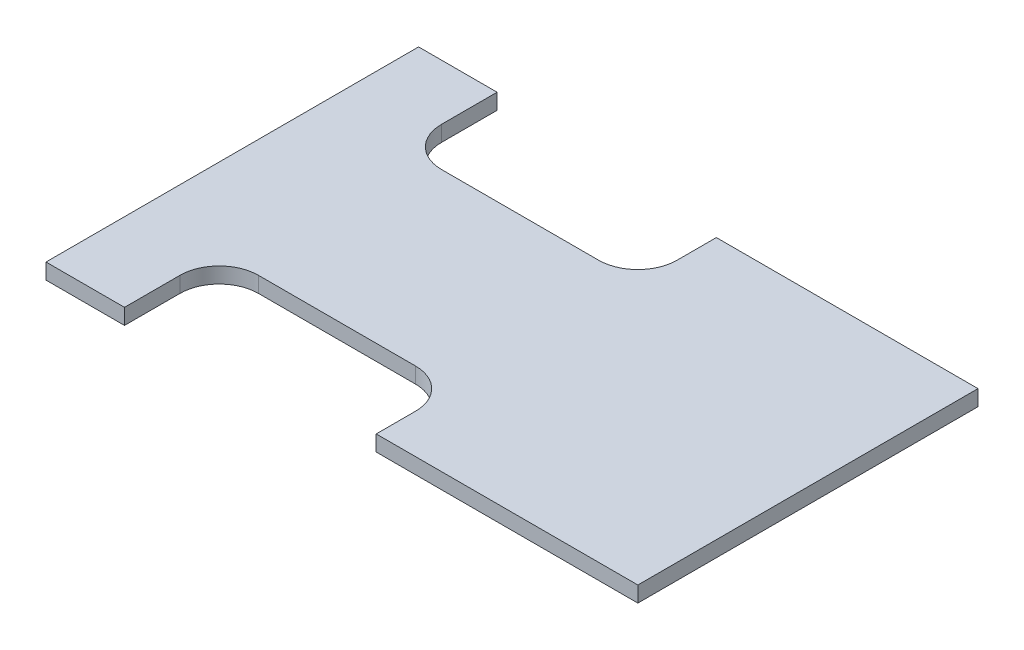
SolidWorks part; units mm, degrees
material "ABS"
ref_plane "Front Plane" through (0, 0, 0) normal (0, 0, 1) x (1, 0, 0)
ref_plane "Top Plane" through (0, 0, 0) normal (0, 1, 0) x (1, 0, 0)
ref_plane "Right Plane" through (0, 0, 0) normal (1, 0, 0) x (0, 0, -1)
sketch "Sketch1" plane through (0, 0, 0) normal (0, 1, 0) x (1, 0, 0)
  line L1 (-110, 65) -> (110, 65)
  line L2 (-110, 65) -> (-110, -65)
  line L3 (-110, -65) -> (110, -65)
  line L4 (110, 65) -> (110, -65)
  line L5 (-110, 65) -> (110, -65) construction
  line L6 (-110, -65) -> (110, 65) construction
  point P0 (0, 0)
  dimension "D1" = 220
  dimension "D2" = 130
extrude "Boss-Extrude1" add sketch "Sketch1" along normal blind 6
sketch "Sketch2" plane through (0, 6, 0) normal (0, 1, 0) x (1, 0, 0)
  line L0 (-110, -65) -> (-80, -65) construction
  line L1 (-110, -65) -> (110, -65) construction
  line L2 (0, 0) -> (-110, 0) construction
  line L3 (-80, -65) -> (10, -65)
  line L4 (-80, -65) -> (-80, -35)
  line L5 (-80, -35) -> (10, -35)
  line L6 (10, -65) -> (10, -35)
  line L7 (-110, 65) -> (-110, -65) construction
  line L8 (-80, 35) -> (10, 35)
  line L9 (10, 65) -> (10, 35)
  line L10 (-80, 65) -> (10, 65)
  line L11 (-80, 65) -> (-80, 35)
  dimension "D1" = 30
  dimension "D2" = 90
  dimension "D3" = 30
extrude "Cut-Extrude1" cut sketch "Sketch2" against normal through all
fillet "Fillet1" radius 15 4 edges at (10, 3, -35) (-80, 3, -35) (-80, 3, 35) (10, 3, 35)
sketch "Sketch3" plane through (0, 6, 0) normal (0, 1, 0) x (1, 0, 0)
  line L0 (0, 0) -> (-110, 0) construction
  line L1 (-80, 65) -> (-110, 65)
  line L2 (-80, 65) -> (-80, 71.2)
  line L3 (-80, 71.2) -> (-110, 71.2)
  line L4 (-110, 65) -> (-110, 71.2)
  line L5 (-110, 65) -> (-110, -65) construction
  line L6 (-80, -71.2) -> (-110, -71.2)
  line L7 (-110, -65) -> (-110, -71.2)
  line L8 (-80, -65) -> (-110, -65)
  line L9 (-80, -65) -> (-80, -71.2)
  dimension "D1" = 6.2
extrude "Boss-Extrude2" add sketch "Sketch3" against normal up to surface (6 mm away) up to face at (-26.25, 0, 0)
